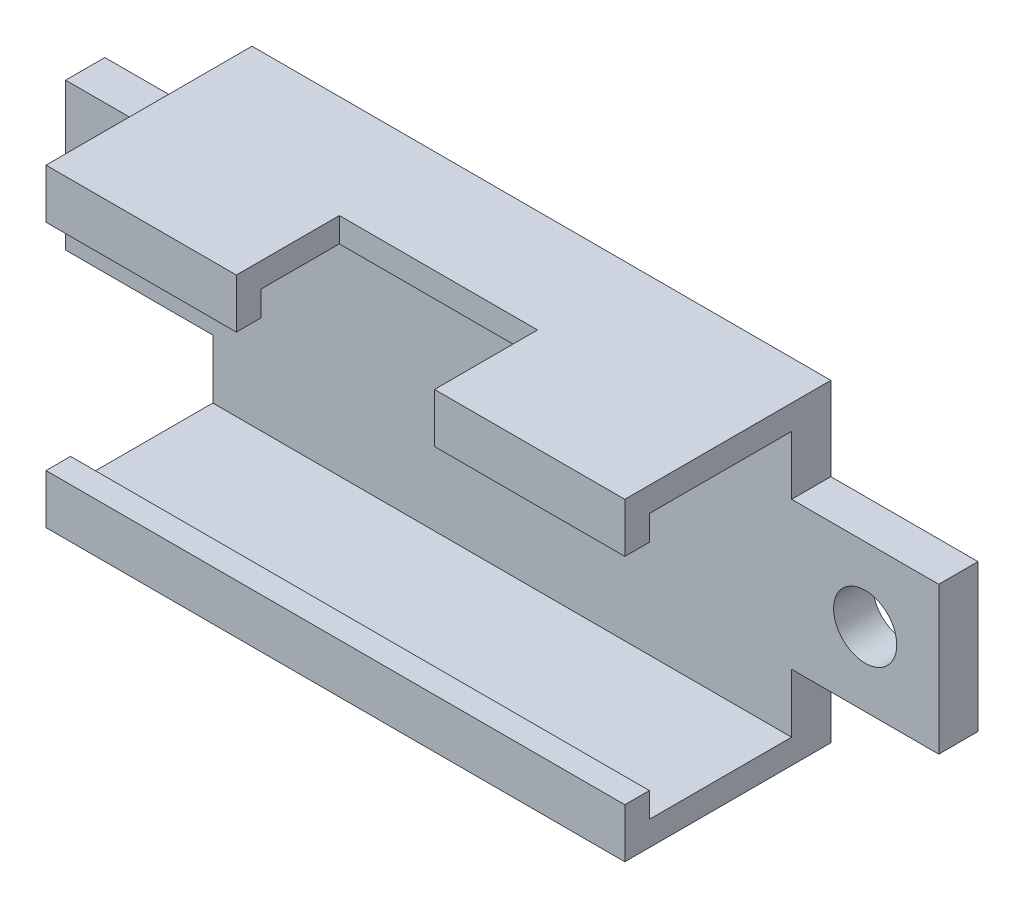
SolidWorks part; units mm, degrees
ref_plane "Front Plane" through (0, 0, 0) normal (0, 0, 1) x (1, 0, 0)
ref_plane "Top Plane" through (0, 0, 0) normal (0, 1, 0) x (1, 0, 0)
ref_plane "Right Plane" through (0, 0, 0) normal (1, 0, 0) x (0, 0, -1)
sketch "Sketch2" plane through (0, 0, 0) normal (0, 0, 1) x (1, 0, 0)
  line L0 (0, 4.25) -> (0, 0)
  line L1 (0, 16) -> (29.5, 16)
  line L2 (0, 16) -> (0, 11.75)
  line L3 (0, 0) -> (29.5, 0)
  line L4 (29.5, 16) -> (29.5, 11.75)
  line L5 (29.5, 11.75) -> (37, 11.75)
  line L7 (29.5, 4.25) -> (37, 4.25)
  line L8 (37, 11.75) -> (37, 4.25)
  line L9 (0, 11.75) -> (-7.5, 11.75)
  line L11 (0, 4.25) -> (-7.5, 4.25)
  line L12 (-7.5, 11.75) -> (-7.5, 4.25)
  line L13 (29.5, 4.25) -> (29.5, 0)
  dimension "D1" = 29.5
  dimension "D2" = 16
  dimension "D3" = 4.25
  dimension "D4" = 4.25
  dimension "D5" = 7.5
  dimension "D6" = 7.5
  dimension "D7" = 7.5
  dimension "D8" = 4.25
extrude "Boss-Extrude2" add sketch "Sketch2" against normal blind 2
sketch "Sketch3" plane through (0, 0, 0) normal (0, 0, 1) x (1, 0, 0)
  line L0 (29.5, 4.25) -> (37, 4.25) construction
  line L1 (37, 4.25) -> (37, 11.75) construction
  line L2 (0, 11.75) -> (-7.5, 11.75) construction
  line L3 (-7.5, 11.75) -> (-7.5, 4.25) construction
  circle A0 centre (33.25, 8) radius 1.61
  circle A1 centre (-3.75, 8) radius 1.61
  dimension "D1" = 3.22
  dimension "D2" = 3.75
  dimension "D4" = 3.22
  dimension "D5" = 3.75
  dimension "D6" = 3.75
  dimension "D3" = 3.75
extrude "Cut-Extrude1" cut sketch "Sketch3" against normal blind 7.62
sketch "Sketch6" plane through (0, 0, 0) normal (0, 0, 1) x (1, 0, 0)
  line L1 (0, 0) -> (29.5, 0)
  line L2 (0, 0) -> (0, 1.25)
  line L3 (0, 1.25) -> (29.5, 1.25)
  line L4 (29.5, 0) -> (29.5, 1.25)
  line L5 (29.5, 11.75) -> (29.5, 16) construction
  line L6 (0, 16) -> (29.5, 16)
  line L7 (0, 16) -> (0, 14.75)
  line L8 (0, 14.75) -> (29.5, 14.75)
  line L9 (29.5, 16) -> (29.5, 14.75)
  dimension "D1" = 29.5
  dimension "D2" = 1.25
  dimension "D3" = 1.25
extrude "Boss-Extrude4" add sketch "Sketch6" along normal blind 8.5
sketch "Sketch7" plane through (0, 14.75, 0) normal (0, -1, 0) x (1, 0, 0)
  line L0 (29.5, -2) -> (29.5, 8.5) construction
  line L1 (0, 8.5) -> (29.5, 8.5)
  line L2 (0, 8.5) -> (0, 7.25)
  line L3 (0, 7.25) -> (29.5, 7.25)
  line L4 (29.5, 8.5) -> (29.5, 7.25)
  dimension "D1" = 1.25
extrude "Boss-Extrude5" add sketch "Sketch7" along normal blind 1.27
ref_axis "Axis1" through (-7.5, 8, 0) along (1, 0, 0)
ref_axis "Axis2" through (37, 8, -2) along (-1, 0, 0)
ref_plane "Plane1" through (0, 8, 0) normal (0, 1, 0) x (1, 0, 0)
mirror "Mirror1" about plane through (0, 8, 0) normal (0, 1, 0) of "Boss-Extrude5"
sketch "Sketch10" plane through (0, 14.75, 0) normal (0, -1, 0) x (1, 0, 0)
  line L12 (0, 8.5) -> (29.5, 8.5) construction
  line L13 (9.7, 8.5) -> (19.8, 8.5)
  line L14 (9.7, 8.5) -> (9.7, 3.25)
  line L15 (9.7, 3.25) -> (19.8, 3.25)
  line L16 (19.8, 8.5) -> (19.8, 3.25)
  line L17 (29.5, -2) -> (29.5, 8.5) construction
  line L18 (0, -2) -> (0, 8.5) construction
  point P6 (19.8, 5.875)
  dimension "D1" = 5.25
  dimension "D2" = 9.7
  dimension "D3" = 9.7
extrude "Cut-Extrude2" cut sketch "Sketch10" against normal mid plane 4
